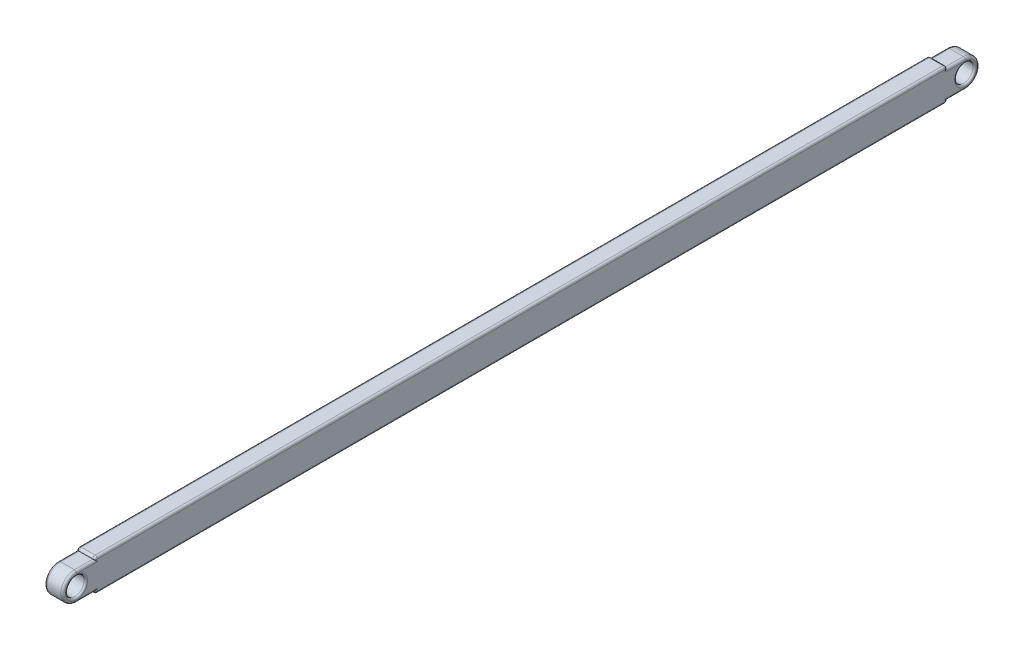
SolidWorks part; units mm, degrees
ref_plane "Front Plane" through (0, 0, 0) normal (0, 0, 1) x (1, 0, 0)
ref_plane "Top Plane" through (0, 0, 0) normal (0, 1, 0) x (1, 0, 0)
ref_plane "Right Plane" through (0, 0, 0) normal (1, 0, 0) x (0, 0, -1)
sketch "Sketch1" plane through (0, 0, 0) normal (1, 0, 0) x (0, 0, -1)
  line L0 (0, 0) -> (0, -0.125)
  line L1 (0, 0) -> (46.5, 0)
  line L2 (0, 0) -> (0, -1.75) construction
  line L3 (0, -1.75) -> (46.5, -1.75)
  line L4 (46.5, 0) -> (46.5, -1.75) construction
  line L5 (0, -0.125) -> (-1, -0.125)
  line L6 (0, -0.125) -> (0, -1.625) construction
  line L7 (0, -1.625) -> (-1, -1.625)
  line L8 (-1, -0.125) -> (-1, -1.625) construction
  line L9 (46.5, -0.125) -> (47.5, -0.125)
  line L10 (46.5, -0.125) -> (46.5, -1.625) construction
  line L11 (46.5, -1.625) -> (47.5, -1.625)
  line L12 (47.5, -0.125) -> (47.5, -1.625) construction
  line L13 (0, -1.625) -> (0, -1.75)
  line L14 (46.5, 0) -> (46.5, -0.125)
  line L15 (46.5, -1.625) -> (46.5, -1.75)
  line L16 (0, -0.875) -> (-1, -0.875) construction
  line L17 (46.5, -0.875) -> (47.5, -0.875) construction
  circle A0 centre (-1, -0.875) radius 0.5
  arc A1 (-1, -1.625) -> (-1, -0.125) centre (-1, -0.875) cw
  circle A2 centre (47.5, -0.875) radius 0.5
  arc A3 (47.5, -0.125) -> (47.5, -1.625) centre (47.5, -0.875) cw
  dimension "D1" = 1
  dimension "D4" = 1
  dimension "D2" = 1.5
  dimension "D3" = 1.5
  dimension "D5" = 48.5
  dimension "D6" = 1.75
  dimension "D7" = 1
  dimension "D8" = 1
extrude "Boss-Extrude1" add sketch "Sketch1" along normal blind 1
fillet "Fillet1" radius 0.125 16 edges at (1, -1.75, -23.25) (0, -1.75, -23.25) (0, 0, -23.25) (1, 0, -23.25) (0, -1.625, -47) (0, -0.875, -48.25) (1, -1.625, -47) (1, -0.875, -48.25) (0, -1.625, 0.5) (0, -0.875, 1.75) (1, -1.625, 0.5) (1, -0.875, 1.75) (0, -0.125, -47) (1, -0.125, -47) (0, -0.125, 0.5) (1, -0.125, 0.5)
fillet "Fillet2" radius 0.1 4 edges at (0, -0.875, 0.5) (1, -0.875, 0.5) (0, -0.875, -48) (1, -0.875, -48)
fillet "Fillet3" radius 0.125 20 edges at (1, -1.5625, 0) (0.9634, -1.7134, 0) (0.5, -1.75, 0) (0.0366, -1.7134, 0) (1, -0.1875, 0) (0.9634, -0.0366, 0) (0.5, 0, 0) (0.0366, -0.0366, 0) (1, -1.5625, -46.5) (0.9634, -1.7134, -46.5) (0.5, -1.75, -46.5) (0.0366, -1.7134, -46.5) (1, -0.1875, -46.5) (0.9634, -0.0366, -46.5) (0.5, 0, -46.5) (0.0366, -0.0366, -46.5) (0, -1.5625, 0) (0, -0.1875, 0) (0, -1.5625, -46.5) (0, -0.1875, -46.5)
